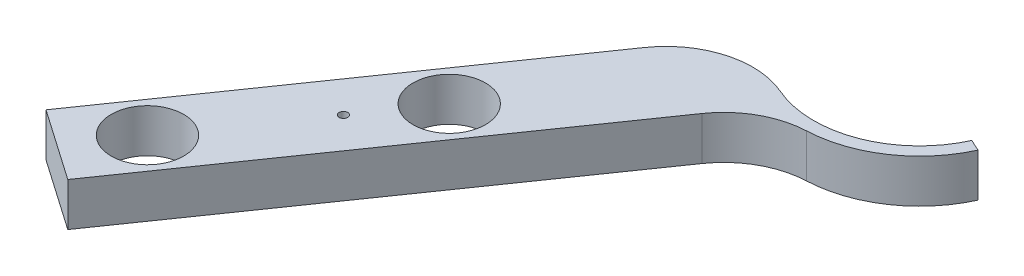
SolidWorks part; units mm, degrees
material "ﾎﾟﾘｴｽﾃﾙ樹脂"
ref_plane "正面" through (0, 0, 0) normal (0, 0, 1) x (1, 0, 0)
ref_plane "平面" through (0, 0, 0) normal (0, 1, 0) x (1, 0, 0)
ref_plane "右側面" through (0, 0, 0) normal (1, 0, 0) x (0, 0, -1)
sketch "ｽｹｯﾁ2" plane through (0, 0, 0) normal (0, 1, 0) x (1, 0, 0)
  line L0 (19.2235, 28.4926) -> (19.2235, 50028.4926) construction
  line L5 (0, 0) -> (-20.9324, -30.1442) construction
  line L6 (-16.4837, -14.9715) -> (8.2699, 20.6753)
  line L7 (-16.4837, -14.9715) -> (-8.2699, -20.6753)
  line L8 (8.2699, 20.6753) -> (16.4837, 14.9715)
  line L9 (-8.2699, -20.6753) -> (16.4837, 14.9715)
  line L10 (-16.4837, -14.9715) -> (16.4837, 14.9715) construction
  line L11 (8.2699, 20.6753) -> (-8.2699, -20.6753) construction
  line L12 (16.4837, 14.9715) -> (16.7754, 15.3916)
  line L13 (16.4837, 14.9715) -> (16.7754, 15.3916)
  line L14 (16.7754, 15.3916) -> (19.2235, 28.8203) construction
  line L15 (-8.2699, -20.6753) -> (-16.8255, -32.996)
  line L16 (-16.8255, -32.996) -> (-25.0394, -27.2923)
  line L17 (-25.0394, -27.2923) -> (-16.4837, -14.9715)
  line L18 (9.5715, 38.4723) -> (28.8755, 19.1683)
  line L19 (0, 0) -> (12.4537, 18.6709) construction
  line L20 (12.4537, 18.6709) -> (17.2984, 15.3067)
  circle A5 centre (19.2235, 28.8203) radius 12.2
  circle A6 centre (19.2235, 28.8203) radius 13.65
  circle A7 centre (-16.6546, -23.9838) radius 4.175
  circle A8 centre (-2.3952, -3.4492) radius 4.175
  point P6 (0, 0)
  dimension "D2" = 24.4
  dimension "D4" = 58.3986
  dimension "D7" = 10.332
  dimension "D8" = 43.3986
  dimension "D9" = 7.5
  dimension "D10" = 25
  dimension "D3" = 27.3
  dimension "D11" = 8.35
  dimension "D1" = 10
  dimension "D5" = 145.223
  dimension "D6" = 45
extrude "ﾎﾞｽ - 押し出し1" add sketch "ｽｹｯﾁ2" along normal blind 5 contours L6 | L6 | L18 A6 L8 L20 A5 | A6 L8 L12 | L8 A6 | A6 L6 L7 L9 L8 A8 | L17 L16 L15 L7 A7 region at (0.2203, 0, -0.3047) region at (-12.5172, 0, 18.0256) region at (5.8688, 0, -29.797) region at (11.6812, 0, -17.9588) region at (16.2326, 0, -15.3484)
fillet "ﾌｨﾚｯﾄ1" radius 20 2 edges at (16.7754, 2.5, -15.3916) (8.2699, 2.5, -20.6753)
sketch "ｽｹｯﾁ6" plane through (0, 5, 0) normal (0, 1, 0) x (1, 0, 0)
  circle A0 centre (-7.4087, -10.6393) radius 0.5
  point P2 (6.1029, 6.7657)
  point P3 (-2.4683, -2.9015)
  point P4 (-7.4087, -10.6393)
  dimension "D1" = 1
extrude "ｶｯﾄ - 押し出し3" cut sketch "ｽｹｯﾁ6" against normal through all
fillet "ﾌｨﾚｯﾄ2" radius 10 1 edges at (17.2984, 2.5, -15.3067)
mirror "ﾐﾗｰ1" about plane through (4.1069, 5, 2.8519) normal (-0.8214, 0, -0.5704) of "ｶｯﾄ - 押し出し3", "ﾎﾞｽ - 押し出し1"
sketch "ｽｹｯﾁ7" plane through (0, 5, 0) normal (0, 1, 0) x (1, 0, 0)
  line L0 (-16.8255, -32.996) -> (31.619, 36.7674)
  line L1 (-8.6117, -38.6998) -> (-25.0394, -27.2923) construction
  line L2 (31.619, 36.7674) -> (6.6354, 54.1163)
  line L3 (6.6354, 54.1163) -> (-41.8092, -15.6471)
  line L4 (-41.8092, -15.6471) -> (-16.8255, -32.996)
extrude "ｶｯﾄ - 押し出し4" cut sketch "ｽｹｯﾁ7" against normal through all
fillet "ﾌｨﾚｯﾄ3" radius 10 2 edges at (24.6975, 2.5, -9.2678) (16.9058, 2.5, -15.5793)
